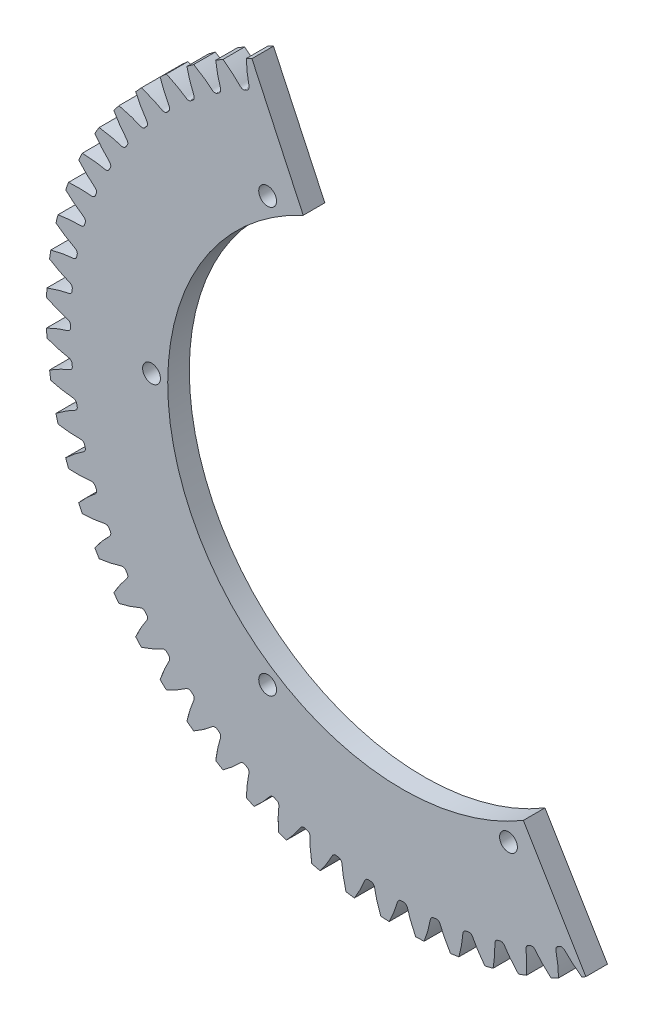
SolidWorks part; units mm, degrees
material "Thornel Mat VMA"
ref_plane "前视基准面" through (0, 0, 0) normal (0, 0, 1) x (1, 0, 0)
ref_plane "上视基准面" through (0, 0, 0) normal (0, 1, 0) x (1, 0, 0)
ref_plane "右视基准面" through (0, 0, 0) normal (1, 0, 0) x (0, 0, -1)
ref_axis "基准轴1" through (0, 0, 55) along (0, 0, -1)
sketch "旋转草图大直齿轮" plane through (0, 0, 0) normal (1, 0, 0) x (0, 0, -1)
  line L0 (0, 0) -> (1, 0) construction
  line L1 (-2, 0) -> (-2, 66)
  line L2 (-2, 66) -> (2, 66)
  line L3 (2, 66) -> (2, 0)
  line L4 (2, 0) -> (-2, 0)
  dimension "D1" = 4
  dimension "D2" = 66
revolve "大直齿轮" add sketch "旋转草图大直齿轮" angle 360 about L0
sketch "齿草图大直齿轮" plane through (0, 0, 0) normal (0, 0, 1) x (1, 0, 0)
  arc A0 (66.0527, 2.4994) -> (66.0527, -2.4994) centre (0, 0) cw
  spline S0 degree 3 poles (66.0527, -2.4994) (66.0103, -2.4781) (65.9469, -2.4464) (65.8623, -2.4046) (65.7994, -2.3737) (65.7367, -2.3431) (65.6744, -2.3129) (65.6123, -2.283) (65.5505, -2.2534) (65.489, -2.2242) (65.4278, -2.1953) (65.3669, -2.1668) (65.3063, -2.1386) (65.246, -2.1107) (65.186, -2.0831) (65.1263, -2.0559) (65.0669, -2.029) (65.0078, -2.0024) (64.949, -1.9761) (64.8905, -1.9502) (64.8323, -1.9246) (64.7745, -1.8993) (64.7169, -1.8743) (64.6596, -1.8496) (64.6027, -1.8252) (64.5461, -1.8012) (64.4898, -1.7774) (64.4338, -1.754) (64.3781, -1.7308) (64.3227, -1.708) (64.2677, -1.6854) (64.2129, -1.6632) (64.1585, -1.6412) (64.1045, -1.6196) (64.0507, -1.5982) (63.9973, -1.5771) (63.9442, -1.5563) (63.8914, -1.5358) (63.839, -1.5156) (63.7868, -1.4957) (63.7351, -1.476) (63.6836, -1.4567) (63.6325, -1.4376) (63.5817, -1.4187) (63.5312, -1.4002) (63.4811, -1.3819) (63.4313, -1.3639) (63.3819, -1.3462) (63.3328, -1.3287) (63.284, -1.3115) (63.2356, -1.2946) (63.1875, -1.2779) (63.1398, -1.2615) (63.0924, -1.2453) (63.0454, -1.2294) (62.9987, -1.2137) (62.9523, -1.1983) (62.9064, -1.1832) (62.8607, -1.1683) (62.8154, -1.1536) (62.7705, -1.1392) (62.7259, -1.125) (62.6816, -1.111) (62.6377, -1.0973) (62.5942, -1.0839) (62.551, -1.0706) (62.5082, -1.0576) (62.4658, -1.0449) (62.4237, -1.0323) (62.3819, -1.02) (62.3405, -1.0079) (62.2995, -0.996) (62.2589, -0.9844) (62.1806, -0.9621) (62.1018, -0.9406) (62.0245, -0.9124) (61.9838, -0.896) (61.9427, -0.8776) (61.9008, -0.8566) (61.8578, -0.8324) (61.8133, -0.804) (61.767, -0.77) (61.7187, -0.7286) (61.669, -0.6777) (61.619, -0.6146) (61.5717, -0.5369) (61.5319, -0.4436) (61.5057, -0.3397) (61.4956, -0.1899) (61.503, 0) (61.4956, 0.1899) (61.5057, 0.3397) (61.5319, 0.4436) (61.5717, 0.5369) (61.619, 0.6146) (61.669, 0.6777) (61.7187, 0.7286) (61.767, 0.77) (61.8133, 0.804) (61.8578, 0.8324) (61.9008, 0.8566) (61.9427, 0.8776) (61.9838, 0.896) (62.0245, 0.9124) (62.1018, 0.9406) (62.1806, 0.9621) (62.2589, 0.9844) (62.2995, 0.996) (62.3405, 1.0079) (62.3819, 1.02) (62.4237, 1.0323) (62.4658, 1.0449) (62.5082, 1.0576) (62.551, 1.0706) (62.5942, 1.0839) (62.6377, 1.0973) (62.6816, 1.111) (62.7259, 1.125) (62.7705, 1.1392) (62.8154, 1.1536) (62.8607, 1.1683) (62.9064, 1.1832) (62.9523, 1.1983) (62.9987, 1.2137) (63.0454, 1.2294) (63.0924, 1.2453) (63.1398, 1.2615) (63.1875, 1.2779) (63.2356, 1.2946) (63.284, 1.3115) (63.3328, 1.3287) (63.3819, 1.3462) (63.4313, 1.3639) (63.4811, 1.3819) (63.5312, 1.4002) (63.5817, 1.4187) (63.6325, 1.4376) (63.6836, 1.4567) (63.7351, 1.476) (63.7868, 1.4957) (63.839, 1.5156) (63.8914, 1.5358) (63.9442, 1.5563) (63.9973, 1.5771) (64.0507, 1.5982) (64.1045, 1.6196) (64.1585, 1.6412) (64.2129, 1.6632) (64.2677, 1.6854) (64.3227, 1.708) (64.3781, 1.7308) (64.4338, 1.754) (64.4898, 1.7774) (64.5461, 1.8012) (64.6027, 1.8252) (64.6596, 1.8496) (64.7169, 1.8743) (64.7745, 1.8993) (64.8323, 1.9246) (64.8905, 1.9502) (64.949, 1.9761) (65.0078, 2.0024) (65.0669, 2.029) (65.1263, 2.0559) (65.186, 2.0831) (65.246, 2.1107) (65.3063, 2.1386) (65.3669, 2.1668) (65.4278, 2.1953) (65.489, 2.2242) (65.5505, 2.2534) (65.6123, 2.283) (65.6744, 2.3129) (65.7367, 2.3431) (65.7994, 2.3737) (65.8623, 2.4046) (65.9469, 2.4464) (66.0103, 2.4781) (66.0527, 2.4994) knots 0 0 0 0 0.012973 0.019403 0.025796 0.032152 0.038471 0.044752 0.050996 0.057202 0.063372 0.069503 0.075598 0.081655 0.087675 0.093658 0.099603 0.105511 0.111382 0.117215 0.123011 0.12877 0.134492 0.140176 0.145823 0.151432 0.157004 0.162539 0.168037 0.173497 0.17892 0.184305 0.189654 0.194965 0.200238 0.205475 0.210674 0.215835 0.22096 0.226047 0.231097 0.236109 0.241084 0.246022 0.250922 0.255786 0.260611 0.2654 0.270151 0.274865 0.279542 0.284181 0.288783 0.293348 0.297875 0.302365 0.306818 0.311233 0.315611 0.319952 0.324255 0.328521 0.33275 0.336942 0.341096 0.345213 0.349292 0.353334 0.357339 0.361307 0.365237 0.36913 0.372986 0.376804 0.391375 0.395308 0.399298 0.403387 0.40763 0.412097 0.416872 0.422064 0.427801 0.434234 0.441516 0.44977 0.459029 0.469155 0.478909 0.5 0.521091 0.530845 0.540971 0.55023 0.558484 0.565766 0.572199 0.577936 0.583128 0.587903 0.59237 0.596613 0.600702 0.604692 0.608625 0.623196 0.627014 0.63087 0.634763 0.638693 0.642661 0.646666 0.650708 0.654787 0.658904 0.663058 0.66725 0.671479 0.675745 0.680048 0.684389 0.688767 0.693182 0.697635 0.702125 0.706652 0.711217 0.715819 0.720458 0.725135 0.729849 0.7346 0.739389 0.744214 0.749078 0.753978 0.758916 0.763891 0.768903 0.773953 0.77904 0.784165 0.789326 0.794525 0.799762 0.805035 0.810346 0.815695 0.82108 0.826503 0.831963 0.837461 0.842996 0.848568 0.854177 0.859824 0.865508 0.87123 0.876989 0.882785 0.888618 0.894489 0.900397 0.906342 0.912325 0.918345 0.924402 0.930497 0.936628 0.942798 0.949004 0.955248 0.961529 0.967848 0.974204 0.980597 0.987027 1 1 1 1
extrude "齿拉伸切除大直齿轮" cut sketch "齿草图大直齿轮" against normal blind 10 and the other way blind 10
pattern_circular "齿形大直齿轮" count 64 every 5.625 about axis through (0, 0, 55) along (0, 0, -1) of "齿拉伸切除大直齿轮"
sketch "孔旋转草图" plane through (0, 0, 0) normal (1, 0, 0) x (0, 0, -1)
  line L0 (0, 0) -> (1, 0) construction
  line L1 (-10, 0) -> (10, 0)
  line L2 (10, 0) -> (10, 5)
  line L3 (10, 5) -> (-10, 5)
  line L4 (-10, 5) -> (-10, 0)
  dimension "TaperSide1" = 5
  dimension "TaperSide2" = 5
revolve "孔旋转切除" cut sketch "孔旋转草图" angle 360 about L0
sketch "辅助草图大直齿轮" plane through (0, 0, 0) normal (0, 0, 1) x (1, 0, 0)
  circle A0 centre (0, 0) radius 64 construction
  circle A1 centre (0, 0) radius 60.1403 construction
  circle A2 centre (0, 0) radius 62.1645 construction
  circle A3 centre (0, 0) radius 66 construction
  circle A4 centre (0, 0) radius 61.5 construction
  dimension "PitchDiameter" = 128
  dimension "BaseDiameter" = 120.2807
  dimension "FormDiameter" = 124.3289
  dimension "MajorDiameter" = 132
  dimension "MinorDiameter" = 123
sketch "草图1" plane through (0, 0, 2) normal (0, 0, 1) x (1, 0, 0)
  line L0 (-24.9844, 39.2177) -> (0, 0) construction
  line L1 (19.6517, 42.1433) -> (0, 0) construction
  line L2 (0, 0) -> (-9.9175, 0) construction
  line L3 (22.4042, 37.2868) -> (33.9925, 56.573)
  line L4 (22.4042, -37.2868) -> (33.9925, -56.573)
  circle A0 centre (0, 0) radius 46.5 construction
  arc A1 (22.4042, 37.2868) -> (22.4042, -37.2868) centre (0, 0) ccw
  circle A2 centre (-24.9844, 39.2177) radius 1.65
  circle A3 centre (-46.5, 0) radius 1.65
  circle A4 centre (19.6517, 42.1433) radius 1.65
  circle A5 centre (19.6517, -42.1433) radius 1.65
  circle A6 centre (-24.9844, -39.2177) radius 1.65
  circle A7 centre (0, 0) radius 66 construction
  arc A8 (33.9925, -56.573) -> (33.9925, 56.573) centre (0, 0) ccw
  dimension "D1" = 93
  dimension "D2" = 87
  dimension "D3" = 3.3
  dimension "D4" = 115
  dimension "D5" = 59
  dimension "D6" = 57.5
extrude "切除-拉伸1" cut sketch "草图1" against normal blind 10
sketch "草图2" plane through (0, 0, 2) normal (0, 0, 1) x (1, 0, 0)
  line L0 (0, 0) -> (33.9925, 56.573)
  line L1 (0, 0) -> (0, -37.574) construction
  line L2 (0, 0) -> (-27.8928, 59.8163)
  line L4 (33.9925, 56.573) -> (22.4042, 37.2868) construction
  circle A0 centre (0, 0) radius 66 construction
  arc A1 (33.9925, 56.573) -> (-27.8928, 59.8163) centre (0, 0) ccw
  dimension "D1" = 25
extrude "切除-拉伸2" cut sketch "草图2" against normal blind 8
